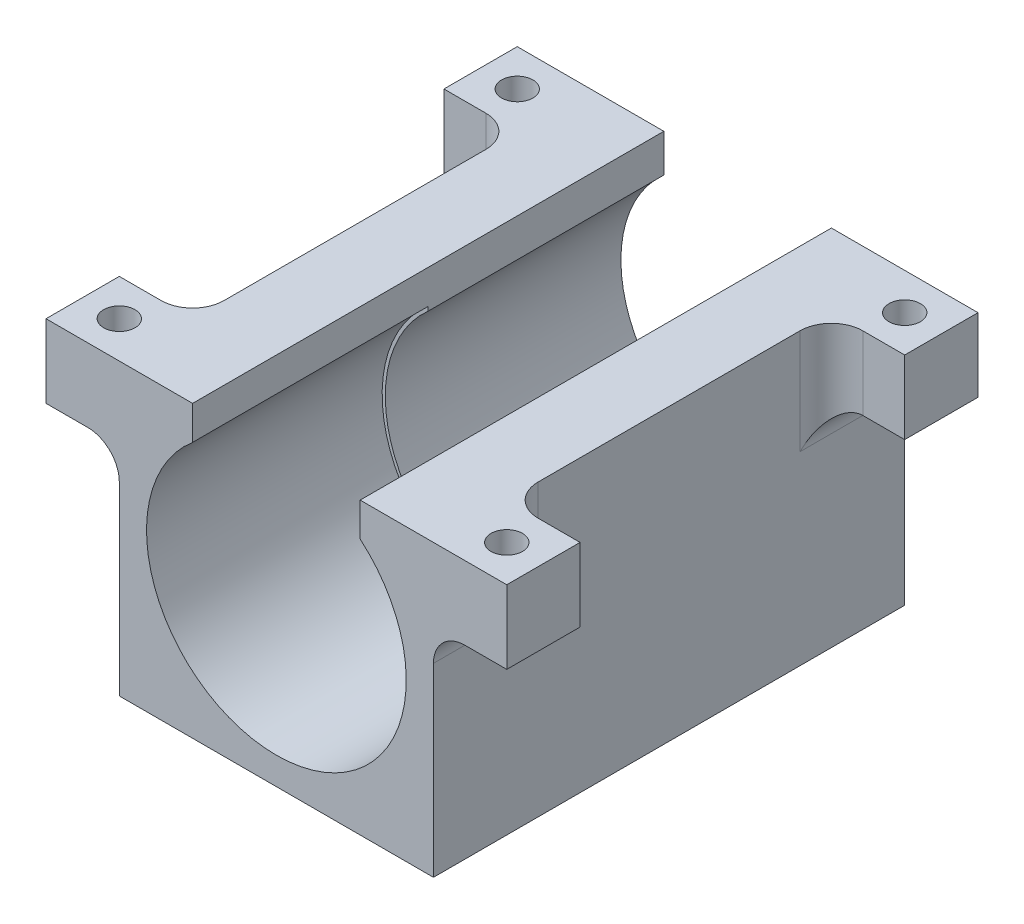
SolidWorks part; units mm, degrees
material "PVC 0.007 Plasticizado"
ref_plane "Plano frontal" through (0, 0, 0) normal (0, 0, 1) x (1, 0, 0)
ref_plane "Plano superior" through (0, 0, 0) normal (0, 1, 0) x (1, 0, 0)
ref_plane "Plano direito" through (0, 0, 0) normal (1, 0, 0) x (0, 0, -1)
sketch "Esboço1" plane through (0, 0, 0) normal (0, 0, 1) x (1, 0, 0)
  line L0 (-28.353, -30.415) -> (1.647, -30.415)
  line L1 (-28.353, -30.415) -> (-28.353, -12.715)
  line L2 (-28.353, -2.715) -> (1.647, -2.715)
  line L3 (1.647, -12.715) -> (1.647, -30.415)
  line L4 (-28.353, -2.715) -> (-35.353, -2.715)
  line L5 (-35.353, -2.715) -> (-35.353, -9.715)
  line L6 (-35.353, -9.715) -> (-31.353, -9.715)
  line L8 (1.647, -2.715) -> (8.647, -2.715)
  line L9 (8.647, -2.715) -> (8.647, -9.715)
  line L10 (8.647, -9.715) -> (4.647, -9.715)
  arc A0 (-28.353, -12.715) -> (-31.353, -9.715) centre (-31.353, -12.715) ccw
  arc A1 (1.647, -12.715) -> (4.647, -9.715) centre (4.647, -12.715) cw
  dimension "D1" = 3
  dimension "D2" = 3
extrude "Ressalto-extrusão2" add sketch "Esboço1" along normal blind 45 contours L2 L4 L5 L6 A0 L1 L0 L3 A1 L10 L9 L8
sketch "Esboço5" plane through (0, 0, 45) normal (0, 0, 1) x (1, 0, 0)
  line L0 (-21.353, -0.4638) -> (-21.353, -12.6412)
  line L1 (-13.353, -0.4638) -> (-5.353, -0.4638)
  line L2 (-13.353, -0.4638) -> (-21.353, -0.4638)
  line L3 (-21.353, -12.6412) -> (-5.353, -12.6412)
  line L4 (-5.353, -0.4638) -> (-5.353, -12.6412)
extrude "Corte-extrusão3" cut sketch "Esboço5" against normal through all
sketch "Esboço6" plane through (0, -30.415, 0) normal (0, -1, 0) x (1, 0, 0)
  line L8 (-31.353, 38) -> (-42.8413, 38)
  line L9 (-31.353, 7) -> (-44.2142, 7)
  line L10 (-28.353, 35) -> (-28.353, 10)
  line L11 (-42.8413, 38) -> (-44.2142, 7)
  line L12 (1.647, 35) -> (1.647, 10)
  line L13 (4.647, 7) -> (17.4486, 7)
  line L14 (4.647, 38) -> (15.1206, 38)
  line L15 (15.1206, 38) -> (17.4486, 7)
  arc A0 (-28.353, 35) -> (-31.353, 38) centre (-31.353, 35) ccw
  arc A1 (1.647, 35) -> (4.647, 38) centre (4.647, 35) cw
  arc A2 (4.647, 7) -> (1.647, 10) centre (4.647, 10) cw
  arc A3 (-28.353, 10) -> (-31.353, 7) centre (-31.353, 10) cw
  line M19 (1.647, 0) -> (1.647, 45)
  dimension "D1" = 3
  dimension "D2" = 3
  dimension "D3" = 3
  dimension "D4" = 3
extrude "Corte-extrusão6" cut sketch "Esboço6" against normal through all contours A2 L13 L15 L14 A1 M19 | L10 A3 L9 L11 L8 A0 region at (9.0385, -30.415, 22.0856)
sketch "Esboço7" plane through (0, -2.715, 0) normal (0, 1, 0) x (1, 0, 0)
  circle A0 centre (-31.853, -3.5) radius 1.5
  circle A1 centre (5.147, -3.5) radius 1.5
  circle A2 centre (5.147, -41.5) radius 1.5
  circle A3 centre (-31.853, -41.5) radius 1.5
extrude "Corte-extrusão7" cut sketch "Esboço7" against normal through all contours A3 | A1 | A2 | A0 region at (-31.853, -2.715, 41.5)
sketch "Esboço8" plane through (0, 0, 45) normal (0, 0, 1) x (1, 0, 0)
  line L0 (-13.353, -30.415) -> (-13.353, -15.415)
  line L1 (-28.353, -30.415) -> (1.647, -30.415) construction
  circle A0 centre (-13.353, -15.415) radius 12.1
  line M2 (-5.353, -2.715) -> (-5.353, -12.6412)
  line M3 (-5.353, -12.6412) -> (-21.353, -12.6412)
  line M4 (-21.353, -12.6412) -> (-21.353, -2.715)
extrude "Corte-extrusão8" cut sketch "Esboço8" against normal through all contours A0 M4 M2 M3 region at (-5.0244, -23.7436, 45)
sketch "Esboço9" plane through (0, 0, 45) normal (0, 0, 1) x (1, 0, 0)
  line L0 (-13.353, -30.415) -> (-13.353, -15.415)
  line L1 (-28.353, -30.415) -> (1.647, -30.415) construction
  circle A0 centre (-13.353, -15.415) radius 12.4
extrude "Corte-extrusão11" cut sketch "Esboço9" against normal blind 22.5 contours A0
